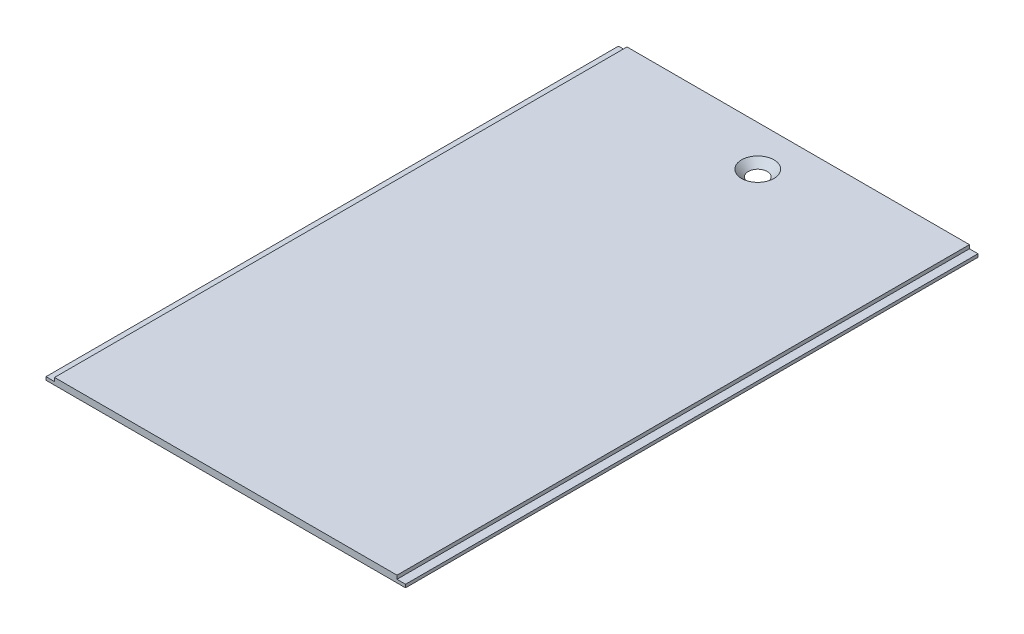
SolidWorks part; units mm, degrees
material "PLA"
ref_plane "Спереди" through (0, 0, 0) normal (0, 0, 1) x (1, 0, 0)
ref_plane "Сверху" through (0, 0, 0) normal (0, 1, 0) x (1, 0, 0)
ref_plane "Справа" through (0, 0, 0) normal (1, 0, 0) x (0, 0, -1)
sketch "Эскиз1" plane through (0, 0, 0) normal (0, 1, 0) x (1, 0, 0)
  line L1 (38.075, 63.65) -> (-38.075, 63.65)
  line L2 (38.075, 63.65) -> (38.075, -63.65)
  line L3 (38.075, -63.65) -> (-38.075, -63.65)
  line L4 (-38.075, 63.65) -> (-38.075, -63.65)
  line L5 (38.075, 63.65) -> (-38.075, -63.65) construction
  line L6 (38.075, -63.65) -> (-38.075, 63.65) construction
  point P0 (0, 0)
  dimension "D1" = 76.15
  dimension "D2" = 127.3
extrude "Бобышка-Вытянуть1" add sketch "Эскиз1" along normal blind 1.5
sketch "Эскиз2" plane through (0, 0, 63.65) normal (0, 0, 1) x (1, 0, 0)
  line L0 (0, 0) -> (0, -50000) construction
  line L1 (-38.075, 0) -> (-39.975, 0)
  line L2 (-38.075, 0) -> (-38.075, 0.7)
  line L3 (-38.075, 0.7) -> (-39.975, 0.7)
  line L4 (-39.975, 0) -> (-39.975, 0.7)
  line L5 (38.075, 0.7) -> (39.975, 0.7)
  line L6 (39.975, 0) -> (39.975, 0.7)
  line L7 (38.075, 0) -> (39.975, 0)
  line L8 (38.075, 0) -> (38.075, 0.7)
  dimension "D1" = 0.7
  dimension "D2" = 1.9
extrude "Бобышка-Вытянуть2" add sketch "Эскиз2" against normal up to surface (127.3 mm away) up to face at (0, 0.75, -63.65)
sketch "Эскиз3" plane through (0, 1.5, 0) normal (0, 1, 0) x (1, 0, 0)
  line L0 (0, 0) -> (0, 50000) construction
  line L1 (38.075, 63.65) -> (-38.075, 63.65) construction
  circle A0 centre (0, 54.65) radius 1.6
  dimension "D1" = 3.2
  dimension "D2" = 9
extrude "Вырез-Вытянуть1" cut sketch "Эскиз3" against normal through all
chamfer "Фаска1" distance 2 angle 45 1 edges at (0, 1.5, -53.05)
